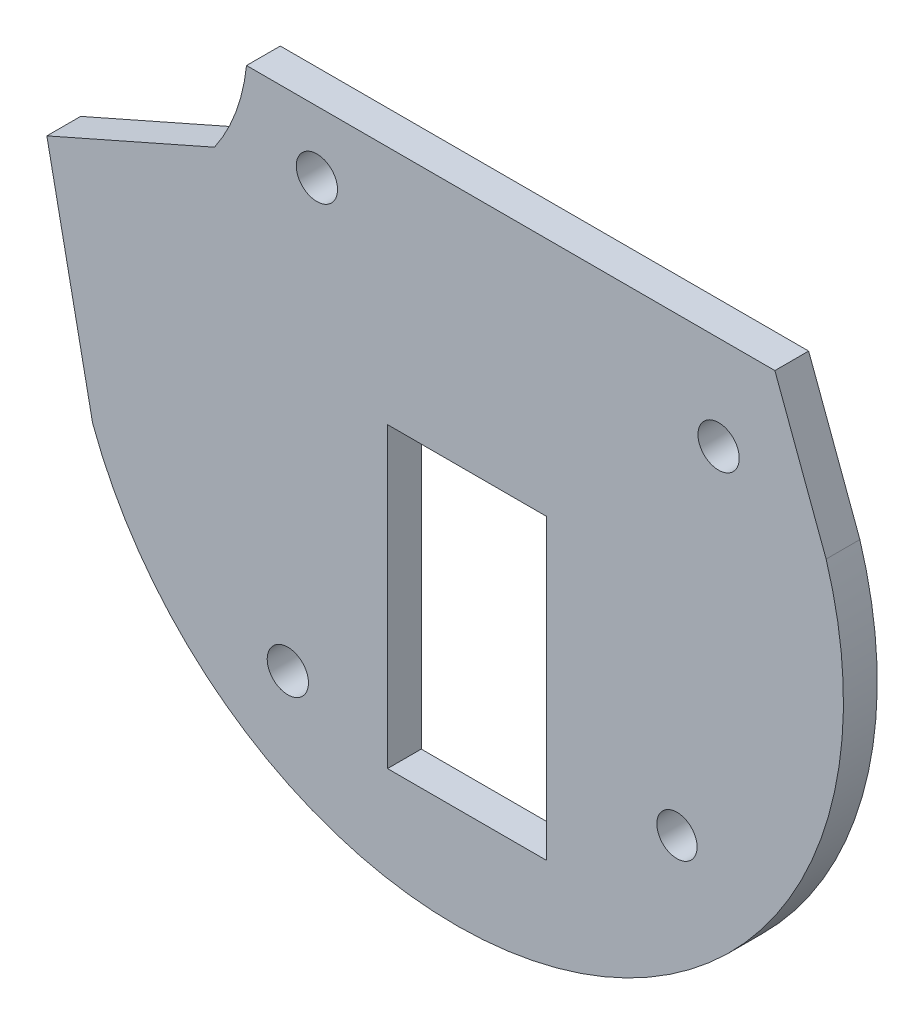
SolidWorks part; units mm, degrees
ref_plane "Front Plane" through (0, 0, 0) normal (0, 0, 1) x (1, 0, 0)
ref_plane "Top Plane" through (0, 0, 0) normal (0, 1, 0) x (1, 0, 0)
ref_plane "Right Plane" through (0, 0, 0) normal (1, 0, 0) x (0, 0, -1)
sketch "Sketch5" plane through (0, 0, 0) normal (0, 0, -1) x (-0.0184, 0.9998, 0)
  line L0 (33.8067, 26.1862) -> (34.4639, -9.5778)
  line L1 (28.6302, -11.8533) -> (23.8302, -23.2927)
  line L2 (23.8302, -23.2927) -> (8.4862, -20.4775)
  line L3 (33.8067, 26.1862) -> (24.4257, 29.4824)
  line L4 (30.1797, -4.8908) -> (34.3764, -4.8137) construction
  line L5 (34.3764, -4.8137) -> (34.4639, -9.5778) construction
  line L6 (34.4639, -9.5778) -> (34.3766, -9.5968) construction
  line L7 (27.5277, 22.2602) -> (33.8767, 22.3769) construction
  line L8 (27.5277, 22.2602) -> (27.4143, 28.4323) construction
  line L9 (3.3631, 18.996) -> (-4.6952, 18.8479) construction
  line L10 (3.3631, 18.996) -> (3.2246, 26.5341) construction
  line L11 (30.1797, -4.8908) -> (30.2892, -10.847) construction
  line L12 (0.3178, -7.4078) -> (0.4754, -15.9798) construction
  line L13 (0.3178, -7.4078) -> (-6.2927, -7.5293) construction
  arc A0 (34.4639, -9.5778) -> (28.6302, -11.8533) centre (36.0016, -22.1359) ccw
  arc A1 (24.4257, 29.4824) -> (8.4862, -20.4775) centre (17.1235, 4.2895) ccw
  circle A2 centre (27.5277, 22.2602) radius 1.397
  circle A3 centre (30.1797, -4.8908) radius 1.397
  circle A4 centre (3.3631, 18.996) radius 1.3622
  circle A5 centre (0.3178, -7.4078) radius 1.397
extrude "Extrude1" add sketch "Sketch5" along normal blind 2.286
sketch "Sketch9" plane through (0, 0, -2.286) normal (0, 0, -1) x (-1, 0, 0)
  line L0 (-25.5606, 34.2821) -> (-4.7199, 34.2821) construction
  line L1 (10.2095, 34.2821) -> (-25.5606, 34.2821) construction
  line L2 (-4.7199, 34.2821) -> (-4.7199, 11.9301) construction
  line L3 (-4.7199, 34.2821) -> (10.2095, 34.2821) construction
  line L4 (7.4124, 0.1817) -> (4.586, 2.9187) construction
sketch "Sketch10" plane through (0, 0, -2.286) normal (0, 0, -1) x (-1, 0, 0)
  line L0 (-4.7199, 11.9301) -> (-4.7199, 13.4541) construction
  line L1 (-4.7199, 10.4061) -> (-7.4821, 10.4061) construction
  line L2 (-7.4821, 10.4061) -> (-7.4821, 13.4541) construction
  line L3 (-7.4821, 13.4541) -> (-1.9576, 13.4541) construction
  line L4 (-1.9576, 13.4541) -> (-1.9576, 10.4061) construction
  line L5 (-1.9576, 10.4061) -> (-4.7199, 10.4061) construction
  line L7 (-4.7199, -2.1669) -> (-10.1047, -2.1669) construction
  line L8 (-4.7199, -2.1669) -> (0.6649, -2.1669) construction
  line L9 (-10.1047, -2.1669) -> (-10.1047, 18.0007) construction
  line L11 (0.6649, 7.9169) -> (0.6649, 18.0007) construction
  line L12 (-10.1047, -2.1669) -> (-10.1047, 18.0007)
  line L13 (-10.1047, 18.0007) -> (0.6649, 18.0007)
  line L14 (0.6649, 7.9169) -> (0.6649, -2.1669) construction
  line L15 (-10.1047, -2.1669) -> (0.6649, -2.1669)
  line L16 (0.6649, -2.1669) -> (0.6649, 18.0007)
  line L17 (-4.7199, 7.9169) -> (20.5583, 7.9169) construction
  line L18 (-4.7199, 7.9169) -> (-4.7199, 11.9301) construction
  arc A0 (-29.0285, 24.9633) -> (20.63, 8.1085) centre (-3.9741, 17.1994) ccw construction
  point P19 (-4.7199, 7.9169)
extrude "Extrude2" cut sketch "Sketch10" against normal up to surface (2.286 mm away) up to face at (17.5688, 3.7116, 0)
